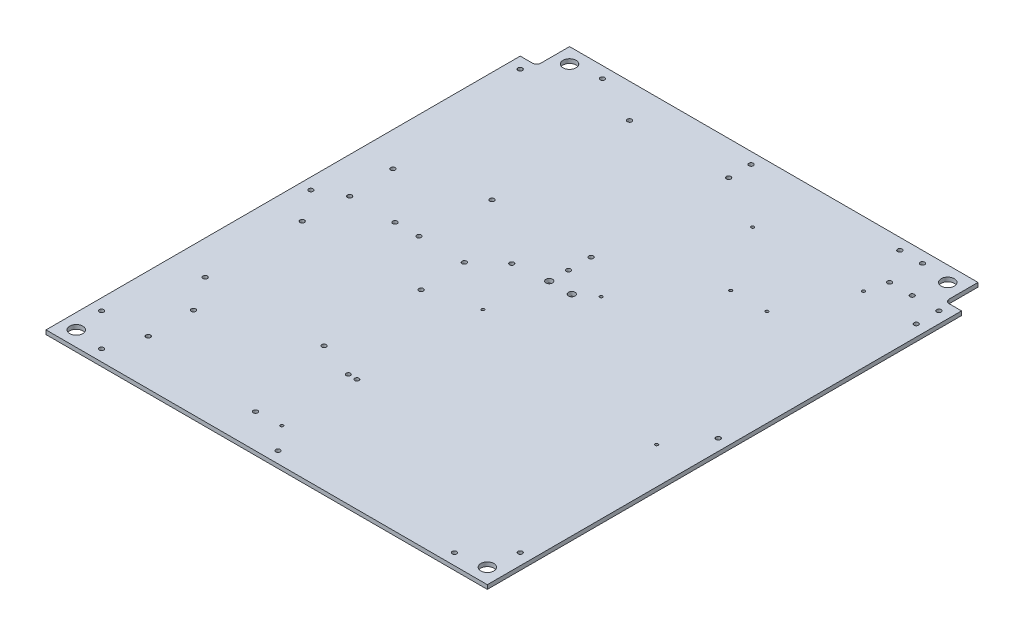
SolidWorks part; units mm, degrees
ref_plane "Front" through (0, 0, 0) normal (0, 0, 1) x (1, 0, 0)
ref_plane "Top" through (0, 0, 0) normal (0, 1, 0) x (1, 0, 0)
ref_plane "Right" through (0, 0, 0) normal (1, 0, 0) x (0, 0, -1)
sketch "Sketch1" plane through (0, 0, 0) normal (0, 1, 0) x (1, 0, 0)
  line L1 (170.434, -195.834) -> (-170.434, -195.834)
  line L2 (170.434, -195.834) -> (170.434, 195.834)
  line L3 (170.434, 195.834) -> (-170.434, 195.834)
  line L4 (-170.434, -195.834) -> (-170.434, 195.834)
  line L5 (170.434, -195.834) -> (-170.434, 195.834) construction
  line L6 (170.434, 195.834) -> (-170.434, -195.834) construction
  point P0 (0, 0)
  dimension "D1" = 340.868
  dimension "D2" = 391.668
extrude "Boss-Extrude1" add sketch "Sketch1" along normal blind 3.175
sketch "Sketch2" plane through (0, 3.175, 0) normal (0, 1, 0) x (1, 0, 0)
  line L0 (170.434, 195.834) -> (-170.434, 195.834) construction
  line L1 (-170.434, 195.834) -> (-157.734, 195.834)
  line L2 (-170.434, 195.834) -> (-170.434, 170.434)
  line L3 (-170.434, 170.434) -> (-160.909, 170.434)
  line L4 (-157.734, 195.834) -> (-157.734, 173.609)
  line L5 (170.434, 195.834) -> (157.734, 195.834)
  line L6 (170.434, 195.834) -> (170.434, 170.434)
  line L7 (170.434, 170.434) -> (160.909, 170.434)
  line L8 (157.734, 195.834) -> (157.734, 173.609)
  arc A0 (-157.734, 173.609) -> (-160.909, 170.434) centre (-160.909, 173.609) cw
  arc A1 (157.734, 173.609) -> (160.909, 170.434) centre (160.909, 173.609) ccw
  dimension "D1" = 3.175
  dimension "D2" = 25.4
  dimension "D3" = 12.7
extrude "Cut-Extrude1" cut sketch "Sketch2" against normal blind 10
hole_wizard "3/8 Clearance Hole1" positions "Sketch3" profile "Sketch4" hole size "3/8" standard "ANSI Inch" end condition through all
sketch "Sketch3" plane through (0, 3.175, 0) normal (0, 1, 0) x (1, 0, 0)
  line L0 (158.75, -184.15) -> (0, -184.15) construction
  line L1 (0, -184.15) -> (-158.75, -184.15) construction
  line L2 (-158.75, -184.15) -> (-158.75, -12.7) construction
  line L3 (-158.75, -12.7) -> (-158.75, 158.75) construction
  line L4 (-158.75, 158.75) -> (158.75, 158.75) construction
  line L5 (158.75, 158.75) -> (158.75, -12.7) construction
  line L6 (158.75, -12.7) -> (158.75, -184.15) construction
  line L8 (146.05, 184.15) -> (0, 184.15) construction
  line L9 (0, 184.15) -> (-146.05, 184.15) construction
  line L10 (-146.05, 184.15) -> (-157.734, 195.834) construction
  line L12 (157.734, 195.834) -> (146.05, 184.15) construction
  line L14 (-158.75, 158.75) -> (-170.434, 170.434) construction
  line L16 (-158.75, -184.15) -> (-170.434, -195.834) construction
  line L18 (158.75, 158.75) -> (170.434, 170.434) construction
  line L20 (158.75, -184.15) -> (170.434, -195.834) construction
  line L21 (158.75, -184.15) -> (158.75, -195.834) construction
  line L22 (-170.434, -195.834) -> (170.434, -195.834) construction
  line L24 (158.75, -184.15) -> (170.434, -184.15) construction
  line L25 (170.434, -195.834) -> (170.434, 170.434) construction
  point P0 (158.75, -184.15)
  point P2 (-158.75, -184.15)
  point P94 (-146.05, 184.15)
  point P96 (146.05, 184.15)
  dimension "D1" = 11.684
sketch "Sketch4" plane through (158.75, 3.175, 184.15) normal (1, 0, 0) x (0, 0, 1)
  line L0 (0, 0) -> (0, 3.175)
  line L1 (0, 3.175) -> (5.0419, 3.175)
  line L2 (5.0419, 3.175) -> (5.0419, 0)
  line L5 (5.0419, 0) -> (0, 0)
  line L11 (0, -6.35) -> (0, 107.95) construction
  dimension "Thru Hole Dia." = 10.0838
  dimension "Thru Hole Depth" = 3.175
hole_wizard "#4-40 Tapped Hole2" positions "Sketch9" profile "Sketch10" tap size "#4-40" standard "ANSI Inch" end condition through all
sketch "Sketch9" plane through (0, 3.175, 0) normal (0, 1, 0) x (1, 0, 0)
  circle A0 centre (33.725, 145.759) radius 1.6319 construction
  circle A1 centre (119.375, 145.759) radius 1.6319 construction
  point P4 (119.375, 145.759)
  point P6 (33.725, 145.759)
  point P20 (21.73, 40.754)
  point P23 (67.7, 94.894)
  point P26 (95.6, 94.894)
  point P30 (-15.34, -13.51)
  point P33 (142.14, -36.73)
  point P36 (142.14, -36.73)
  point P39 (-15.34, -168.81)
cosmetic thread "Hole Thread17" parameters "D2"=2.8448
cosmetic thread "Hole Thread18" parameters "D2"=2.8448
sketch "Sketch10" plane through (119.375, 3.175, -145.759) normal (1, 0, 0) x (0, 0, 1)
  line L0 (0, 0) -> (0, 3.175)
  line L1 (0, 3.175) -> (1.1303, 3.175)
  line L2 (1.1303, 3.175) -> (1.1303, 0)
  line L5 (1.1303, 0) -> (0, 0)
  line L11 (0, -6.35) -> (0, 107.95) construction
  dimension "Thru Tap Drill Dia." = 2.2606
  dimension "Thru Tap Drill Depth" = 3.175
cosmetic thread "Hole Thread19" parameters "D2"=2.8448
cosmetic thread "Hole Thread20" parameters "D2"=2.8448
cosmetic thread "Hole Thread21" parameters "D2"=2.8448
cosmetic thread "Hole Thread22" parameters "D2"=2.8448
cosmetic thread "Hole Thread23" parameters "D2"=2.8448
cosmetic thread "Hole Thread24" parameters "D2"=2.8448
cosmetic thread "Hole Thread25" parameters "D2"=2.8448
hole_wizard "#8-32 Tapped Hole2" positions "Sketch13" profile "Sketch14" tap size "#8-32" standard "ANSI Inch" end condition through all
sketch "Sketch13" plane through (0, 3.175, 0) normal (0, 1, 0) x (1, 0, 0)
  line L34 (-161.684, 161.684) -> (-161.684, -161.684)
  line L36 (161.684, 144.184) -> (161.684, -161.684)
  line L38 (-123.584, 187.084) -> (106.084, 187.084)
  line L39 (106.084, 187.084) -> (123.584, 187.084)
  line L40 (123.584, 187.084) -> (123.584, 161.684)
  line L42 (123.584, 161.684) -> (141.084, 161.684)
  line L43 (141.084, 161.684) -> (161.684, 161.684)
  line L45 (161.684, 161.684) -> (161.684, 144.184)
  line L47 (-8.584, 187.084) -> (-8.584, 169.584)
  line L48 (-8.584, 169.584) -> (-8.584, 63.334)
  line L50 (-8.584, 63.334) -> (-8.584, 45.834)
  line L51 (-8.584, 45.834) -> (-144.184, 45.834)
  line L52 (-144.184, 45.834) -> (-161.684, 45.834)
  line L54 (-34.884, 45.834) -> (-34.884, 28.334)
  line L55 (-34.884, 28.334) -> (-34.884, -169.584)
  line L56 (-34.884, -169.584) -> (-34.884, -187.084)
  line L58 (-136.284, -187.084) -> (136.284, -187.084)
  line L60 (-161.684, -24.166) -> (-144.184, -24.166)
  line L61 (-144.184, -24.166) -> (-52.384, -24.166)
  line L62 (-52.384, -24.166) -> (-34.884, -24.166)
  line L64 (-161.684, -99.166) -> (-144.184, -99.166)
  line L65 (-144.184, -99.166) -> (-52.384, -99.166)
  line L66 (-52.384, -99.166) -> (-34.884, -99.166)
  line L68 (-161.684, 10.834) -> (-142.534, 10.834)
  line L69 (-142.534, 10.834) -> (-107.534, 10.834)
  line L70 (-107.534, 10.834) -> (-89.034, 10.834)
  line L71 (-89.034, 10.834) -> (-54.034, 10.834)
  line L72 (-54.034, 10.834) -> (-34.884, 10.834)
  line L74 (-85.134, 45.834) -> (-85.134, 63.334)
  line L75 (-85.134, 63.334) -> (-85.134, 169.584)
  line L76 (-85.134, 169.584) -> (-85.134, 187.084)
  line L78 (-170.434, 170.434) -> (-170.434, -195.834) construction
  line L79 (157.734, 195.834) -> (-157.734, 195.834) construction
  line L81 (170.434, -195.834) -> (170.434, 170.434) construction
  line L82 (-170.434, -195.834) -> (170.434, -195.834) construction
  line L83 (-170.434, 170.434) -> (-160.909, 170.434) construction
  line L84 (160.909, 170.434) -> (170.434, 170.434) construction
  line L85 (157.734, 195.834) -> (157.734, 173.609) construction
  line L86 (-157.734, 173.609) -> (-157.734, 195.834) construction
  line L87 (-76.384, 45.834) -> (-76.384, 10.834) construction
  line L88 (-76.384, 10.834) -> (-76.384, -24.166) construction
  line L90 (-161.684, 63.334) -> (-85.134, 63.334) construction
  line L92 (-85.134, 63.334) -> (-8.584, 63.334) construction
  line L93 (-126.684, -99.166) -> (-126.684, -125.625)
  line L94 (-126.684, -125.625) -> (-126.684, -160.625)
  line L95 (-126.684, -160.625) -> (-126.684, -187.084)
  point P146 (-161.684, -161.684)
  point P148 (-161.684, 0)
  point P150 (-161.684, 161.684)
  point P152 (-144.184, 45.834)
  point P154 (-8.584, 45.834)
  point P156 (-144.184, -24.166)
  point P158 (-52.384, -24.166)
  point P160 (-144.184, -99.166)
  point P162 (-52.384, -99.166)
  point P164 (-34.884, 28.334)
  point P166 (-34.884, -169.584)
  point P168 (-136.284, -187.084)
  point P170 (0, -187.084)
  point P172 (136.284, -187.084)
  point P174 (161.684, -161.684)
  point P176 (161.684, -8.75)
  point P178 (161.684, 144.184)
  point P180 (141.084, 161.684)
  point P182 (161.684, 161.684)
  point P184 (123.584, 161.684)
  point P186 (123.584, 187.084)
  point P188 (106.084, 187.084)
  point P190 (-123.584, 187.084)
  point P192 (-8.75, 187.084)
  point P194 (-8.584, 169.584)
  point P196 (-8.584, 63.334)
  point P198 (-142.534, 10.834)
  point P200 (-107.534, 10.834)
  point P202 (-89.034, 10.834)
  point P204 (-54.034, 10.834)
  point P206 (-85.134, 63.334)
  point P208 (-85.134, 169.584)
  point P345 (-126.684, -125.625)
  point P347 (-126.684, -160.625)
  point P350 (0, 0)
  point P351 (0, 0)
  dimension "D1" = 8.75
  dimension "D2" = 8.75
  dimension "D3" = 8.75
  dimension "D4" = 8.75
  dimension "D5" = 34.15
  dimension "D6" = 8.75
  dimension "D7" = 8.75
  dimension "D8" = 17.5
  dimension "D9" = 34.15
  dimension "D10" = 17.5
  dimension "D11" = 17.5
  dimension "D12" = 34.15
  dimension "D13" = 34.15
  dimension "D14" = 34.15
  dimension "D15" = 34.15
  dimension "D16" = 17.5
  dimension "D17" = 17.5
  dimension "D18" = 17.5
  dimension "D19" = 17.5
  dimension "D20" = 17.5
  dimension "D21" = 17.5
  dimension "D22" = 17.5
  dimension "D23" = 17.5
  dimension "D24" = 150
  dimension "D25" = 161.85
  dimension "D26" = 135.55
  dimension "D27" = 70
  dimension "D28" = 75
  dimension "D29" = 35
  dimension "D30" = 35
  dimension "D31" = 53.5
  dimension "D32" = 35
  dimension "D33" = 35
sketch "Sketch14" plane through (-161.684, 3.175, 161.684) normal (1, 0, 0) x (0, 0, 1)
  line L0 (0, 0) -> (0, 3.175)
  line L1 (0, 3.175) -> (1.7272, 3.175)
  line L2 (1.7272, 3.175) -> (1.7272, 0)
  line L5 (1.7272, 0) -> (0, 0)
  line L11 (0, -6.35) -> (0, 107.95) construction
  dimension "Thread Major Dia." = 3.4544
  dimension "Thru Tap Drill Depth" = 3.175
hole_wizard "#4 Clearance Hole1" positions "Sketch15" profile "Sketch16" hole size "#4" standard "ANSI Inch"
sketch "Sketch15" plane through (0, 3.175, 0) normal (0, 1, 0) x (1, 0, 0)
  point P0 (-23.9256, -108.8644)
  point P3 (-17.2744, -108.8644)
sketch "Sketch16" plane through (-23.9256, 3.175, 108.8644) normal (1, 0, 0) x (0, 0, 1)
  line L0 (0, 0) -> (0, 8.9906)
  line L1 (0, 8.9906) -> (1.6319, 8.01)
  line L2 (1.6319, 8.01) -> (1.6319, 0)
  line L5 (1.6319, 0) -> (0, 0)
  line L10 (0, 8.9906) -> (-1.632, 8.01) construction
  line L11 (0, -6.35) -> (0, 107.95) construction
  dimension "Hole Dia." = 3.2639
  dimension "Hole Depth" = 8.01
  dimension "Drill Angle" = 118
hole_wizard "#10 Clearance Hole1" positions "Sketch17" profile "Sketch18" hole size "#10" standard "ANSI Inch" end condition through all
sketch "Sketch17" plane through (0, 0, 0) normal (0, -1, 0) x (-1, 0, 0)
  circle A0 centre (-8.7376, 31.1216) radius 2.032 construction
  circle A1 centre (8.7376, 31.1216) radius 2.032 construction
  point P0 (8.7376, 31.1216)
  point P2 (-8.7376, 31.1216)
  point P5 (-5.085, 22.484)
sketch "Sketch18" plane through (-8.7376, 0, -31.1216) normal (1, 0, 0) x (0, 0, -1)
  line L0 (0, 0) -> (0, 3.175)
  line L1 (0, 3.175) -> (2.5527, 3.175)
  line L2 (2.5527, 3.175) -> (2.5527, 0)
  line L5 (2.5527, 0) -> (0, 0)
  line L11 (0, -6.35) -> (0, 107.95) construction
  dimension "Thru Hole Dia." = 5.1054
  dimension "Thru Hole Depth" = 3.175
